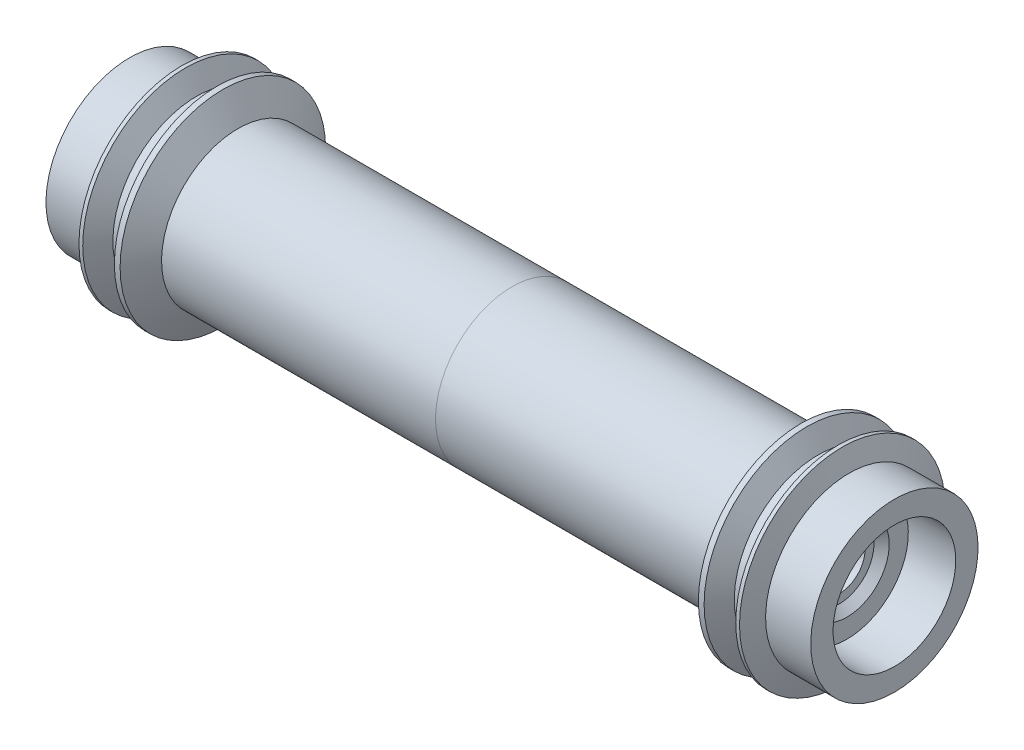
SolidWorks part; units mm, degrees
ref_plane "Front Plane" through (0, 0, 0) normal (0, 0, 1) x (1, 0, 0)
ref_plane "Top Plane" through (0, 0, 0) normal (0, 1, 0) x (1, 0, 0)
ref_plane "Right Plane" through (0, 0, 0) normal (1, 0, 0) x (0, 0, -1)
sketch "Sketch2" plane through (0, 0, 0) normal (0, 0, 1) x (1, 0, 0)
  line L0 (0, 0) -> (0, 28.4375) construction
  line L1 (-25.4, 4.075) -> (-22.25, 4.075) construction
  line L2 (-25.4, 4.075) -> (-25.4, -4.075) construction
  line L3 (-25.4, -4.075) -> (-22.25, -4.075) construction
  line L4 (-22.25, 4.075) -> (-22.25, -4.075) construction
  line L5 (-25.4, 4.075) -> (-22.25, -4.075) construction
  line L6 (-25.4, -4.075) -> (-22.25, 4.075) construction
  line L7 (22.25, 4.5) -> (41.3332, 4.5) construction
  line L8 (22.25, 4.5) -> (22.25, -4.5) construction
  line L9 (22.25, -4.5) -> (41.3332, -4.5) construction
  line L10 (41.3332, 4.5) -> (41.3332, -4.5) construction
  line L11 (22.25, 4.5) -> (41.3332, -4.5) construction
  line L12 (22.25, -4.5) -> (41.3332, 4.5) construction
  line L13 (-25.4, 0) -> (41.3332, 0) construction
  line L14 (-25.4, 5.5562) -> (-22.4, 5.5562)
  line L15 (-22.4, 5.5562) -> (-21.9378, 6.8262)
  line L16 (-21.9378, 6.8262) -> (-21.6882, 6.8262)
  line L19 (-19.5868, 6.8262) -> (-19.2058, 6.8262)
  line L20 (-19.2058, 6.8262) -> (-18.1976, 5.08)
  line L21 (-18.1976, 5.08) -> (0, 5.08)
  line L22 (-25.4, 5.5562) -> (-25.4, 4.075)
  line L23 (-25.4, 4.075) -> (-22.25, 4.075)
  line L24 (-22.25, 4.075) -> (-22.25, 0)
  line L25 (-22.25, 0) -> (0, 0)
  line L26 (0, 0) -> (0, 5.08)
  line L27 (-33.5594, -5.5562) -> (-33.5594, 5.5562) construction
  line L28 (-20.6375, 5.5562) -> (-20.6375, 7.68) construction
  line L29 (-20.6375, 5.5562) -> (20.6375, 5.5562) construction
  line L30 (-25.4, 5.5562) -> (25.4, 5.5562) construction
  line L31 (0, 1.6) -> (-12.5, 1.6)
  line L32 (-12.5, 1.6) -> (-14.1, 0)
  line L33 (-12.5, 1.6) -> (-12.5, -1.6) construction
  line L34 (-12.5, 1.6) -> (12.5, 1.6) construction
  line L35 (-22.25, 1.7145) -> (-15.575, 1.7145)
  line L36 (-15.575, 1.7145) -> (-15.575, 0)
  line L37 (-22.25, 2.805) -> (-21.742, 2.297)
  line L38 (-15.575, 1.7145) -> (-28.575, 1.7145) construction
  line L39 (-15.575, 1.7145) -> (-15.575, -1.7145) construction
  line L40 (-15.575, -1.7145) -> (-28.575, -1.7145) construction
  line L41 (-28.575, 1.7145) -> (-28.575, -1.7145) construction
  line L42 (-21.742, 2.297) -> (-21.742, 0)
  line L43 (-20.955, 5.5562) -> (-20.32, 5.5562)
  line L44 (-20.32, 5.5562) -> (-19.5868, 6.8262)
  line L45 (-21.6882, 6.8262) -> (-20.955, 5.5562)
  point P0 (-23.825, 0)
  point P5 (31.7916, 0)
  point P27 (-33.5594, 0)
  point P28 (-19.3963, 6.8262)
  point P29 (-12.5, 0)
  point P33 (0, 5.5562)
  point P36 (0, 1.6)
  point P48 (-15.575, 0)
  point P51 (0, 5.5562)
  point P54 (-20.6375, 5.5562)
  dimension "D1" = 3.15
  dimension "D3" = 5.08
  dimension "D4" = 11.1125
  dimension "D5" = 8.15
  dimension "D6" = 60
  dimension "D7" = 60
  dimension "D8" = 1.27
  dimension "D9" = 70
  dimension "D10" = 41.275
  dimension "D11" = 50.8
  dimension "D12" = 0.381
  dimension "D13" = 45
  dimension "D14" = 25
  dimension "D15" = 3.2
  dimension "D16" = 3.429
  dimension "D17" = 3.175
  dimension "D18" = 1.27
  dimension "D19" = 0.508
  dimension "D20" = 45
  dimension "D21" = 13
  dimension "D22" = 3
  dimension "D23" = 0.635
revolve "Revolve1" add sketch "Sketch2" angle 360 about L13 region at (-12.2585, 3.4548, 0)
mirror "Mirror1" about plane through (0, 0, 0) normal (1, 0, 0) of bodies 101
chamfer "Chamfer1" distance 0.508 angle 45 1 edges at (-25.4, -4.075, 0)
